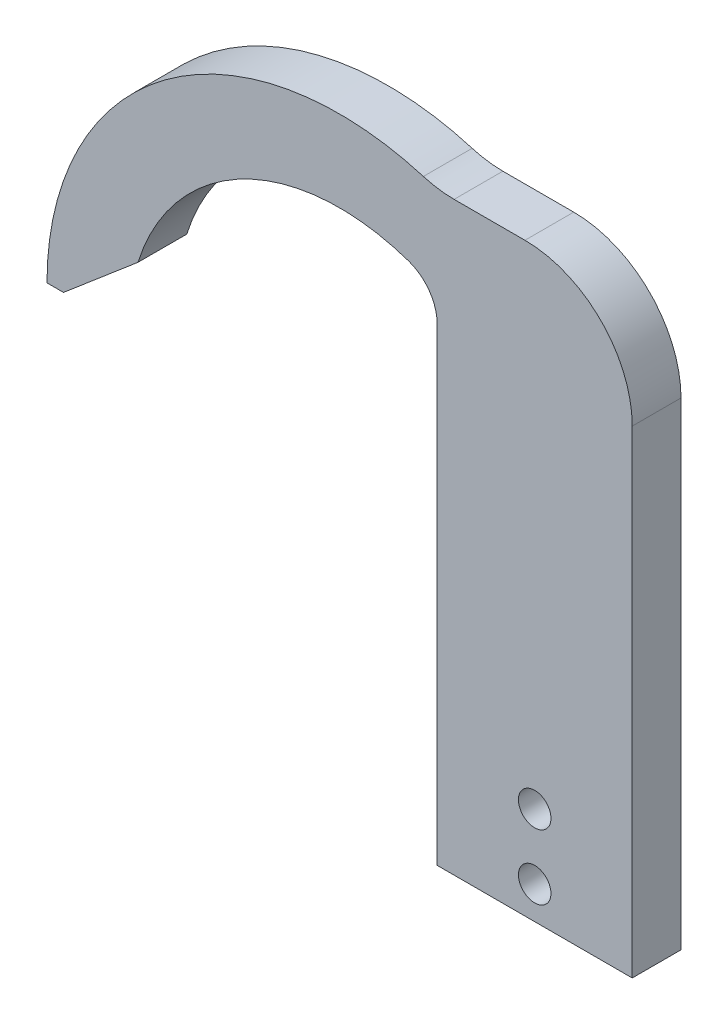
SolidWorks part; units mm, degrees
material "6063-T1"
ref_plane "Front Plane" through (0, 0, 0) normal (0, 0, 1) x (1, 0, 0)
ref_plane "Top Plane" through (0, 0, 0) normal (0, 1, 0) x (1, 0, 0)
ref_plane "Right Plane" through (0, 0, 0) normal (1, 0, 0) x (0, 0, -1)
sketch "Sketch1" plane through (0, 0, 0) normal (0, 0, 1) x (1, 0, 0)
  line L0 (0, 57.15) -> (0, -57.15) construction
  line L1 (-19.05, 57.15) -> (19.05, 57.15)
  line L2 (-19.05, 57.15) -> (-19.05, -57.15)
  line L3 (-19.05, -57.15) -> (19.05, -57.15)
  line L4 (19.05, 57.15) -> (19.05, -57.15)
  line L5 (-19.05, 57.15) -> (19.05, -57.15) construction
  line L6 (-19.05, -57.15) -> (19.05, 57.15) construction
  line L7 (-95.25, 3.2685) -> (19.05, 3.2685) construction
  line L8 (-95.25, 3.2685) -> (-79.375, 3.2685)
  line L10 (19.05, -14.7451) -> (19.05, -143.545) construction
  circle A0 centre (-38.1, 3.2685) radius 57.15
  circle A1 centre (-38.1, 3.2685) radius 41.275
  point P0 (0, 0)
  point P19 (0, 0)
  point P20 (-25.4, -84.1026)
  dimension "D3" = 114.3
  dimension "D4" = 82.55
  dimension "D1" = 38.1
  dimension "D2" = 114.3
extrude "Boss-Extrude1" add sketch "Sketch1" along normal blind 9.525 contours A1 L2 A0 L8 | A0 L4 L1 | A1 L2 A0 | L2 A1 | A0 L2 L3 L4 region at (7.6295, 35.6041, 0) region at (8.8019, 44.7243, 0) region at (-61.364, 38.1607, 0) region at (-9.9164, 3.2685, 0) region at (6.0785, -43.0434, 0)
fillet "Fillet1" radius 8.255 1 edges at (-19.05, 39.8843, 4.7625)
chamfer "Chamfer1" distance 15.24 angle 48 1 edges at (-79.375, 3.2685, 4.7625) first distance on face at (-87.3125, 3.2685, 4.7625)
fillet "Fillet3" radius 20.955 2 edges at (-19.05, 57.15, 4.7625) (19.05, 57.15, 4.7625)
sketch "Sketch2" plane through (0, 0, 9.525) normal (0, 0, 1) x (1, 0, 0)
  line L0 (-19.05, -57.15) -> (19.05, -57.15) construction
  circle A0 centre (0, -50.8) radius 3.175
  circle A1 centre (0, -38.1) radius 3.175
  dimension "D3" = 6.35
  dimension "D4" = 6.35
  dimension "D1" = 6.35
  dimension "D2" = 12.7
extrude "Cut-Extrude1" cut sketch "Sketch2" against normal through all
